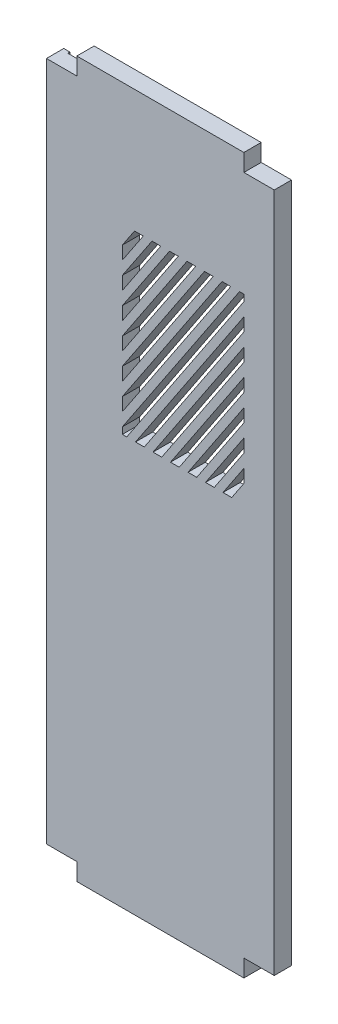
SolidWorks part; units mm, degrees
ref_plane "Front Plane" through (0, 0, 0) normal (0, 0, 1) x (1, 0, 0)
ref_plane "Top Plane" through (0, 0, 0) normal (0, 1, 0) x (1, 0, 0)
ref_plane "Right Plane" through (0, 0, 0) normal (1, 0, 0) x (0, 0, -1)
sketch "Sketch1" plane through (0, 0, 0) normal (0, 0, 1) x (1, 0, 0)
  line L1 (0, 0) -> (75, 0)
  line L2 (0, 0) -> (0, 235.4)
  line L3 (0, 235.4) -> (75, 235.4)
  line L4 (75, 0) -> (75, 235.4)
  dimension "D1" = 235.4
  dimension "D2" = 75
extrude "Boss-Extrude1" add sketch "Sketch1" along normal blind 5.7
sketch "Sketch2" plane through (0, 0, 0) normal (0, 0, -1) x (-1, 0, 0)
  line L2 (-75, 0) -> (-65, 0)
  line L3 (-75, 0) -> (-75, 5.7)
  line L4 (-75, 5.7) -> (-65, 5.7)
  line L6 (-65, 0) -> (-65, 5.7)
  line L7 (0, 0) -> (-10, 0)
  line L8 (0, 0) -> (0, 5.7)
  line L9 (0, 5.7) -> (-10, 5.7)
  line L12 (-10, 0) -> (-10, 5.7)
  line L13 (0, 235.4) -> (-10, 235.4)
  line L14 (0, 235.4) -> (0, 229.7)
  line L15 (0, 229.7) -> (-10, 229.7)
  line L16 (-10, 235.4) -> (-10, 229.7)
  line L17 (-75, 235.4) -> (-65, 235.4)
  line L18 (-75, 235.4) -> (-75, 229.7)
  line L19 (-75, 229.7) -> (-65, 229.7)
  line L20 (-65, 235.4) -> (-65, 229.7)
  dimension "D1" = 5.7
  dimension "D2" = 5.7
  dimension "D3" = 10
  dimension "D4" = 10
  dimension "D5" = 10
  dimension "D6" = 5.7
  dimension "D7" = 5.7
  dimension "D8" = 10
extrude "Cut-Extrude1" cut sketch "Sketch2" against normal blind 5.7
sketch "Sketch3" plane through (0, 0, 5.7) normal (0, 0, 1) x (1, 0, 0)
  line L1 (75, 5.7) -> (75, 229.7) construction
  line L39 (65, 195) -> (25, 135) construction
  line L40 (25, 195) -> (65, 195)
  line L41 (25, 195) -> (25, 135)
  line L42 (25, 135) -> (65, 135)
  line L43 (65, 195) -> (65, 135)
  line L44 (63.5578, 195) -> (25, 137.1633)
  line L45 (65, 192.8367) -> (26.4422, 135)
  line L46 (45, 165) -> (25, 165) construction
  line L47 (45, 165) -> (65, 165) construction
  line L48 (60.6778, 195) -> (25, 141.4833)
  line L49 (57.7978, 195) -> (25, 145.8033)
  line L50 (54.9178, 195) -> (25, 150.1233)
  line L51 (52.0378, 195) -> (25, 154.4433)
  line L52 (49.1578, 195) -> (25, 158.7633)
  line L53 (46.2778, 195) -> (25, 163.0833)
  line L54 (43.3978, 195) -> (25, 167.4033)
  line L55 (40.5178, 195) -> (25, 171.7233)
  line L56 (37.6378, 195) -> (25, 176.0433)
  line L57 (34.7578, 195) -> (25, 180.3633)
  line L58 (31.8778, 195) -> (25, 184.6833)
  line L59 (28.9978, 195) -> (25, 189.0033)
  line L60 (26.1178, 195) -> (25, 193.3233)
  line L61 (65, 188.5167) -> (29.3222, 135)
  line L62 (65, 184.1967) -> (32.2022, 135)
  line L63 (65, 179.8767) -> (35.0822, 135)
  line L64 (65, 175.5567) -> (37.9622, 135)
  line L65 (65, 171.2367) -> (40.8422, 135)
  line L66 (65, 166.9167) -> (43.7222, 135)
  line L67 (65, 162.5967) -> (46.6022, 135)
  line L68 (65, 158.2767) -> (49.4822, 135)
  line L69 (65, 153.9567) -> (52.3622, 135)
  line L70 (65, 149.6367) -> (55.2422, 135)
  line L71 (65, 145.3167) -> (58.1222, 135)
  line L72 (65, 140.9967) -> (61.0022, 135)
  line L73 (65, 136.6767) -> (63.8822, 135)
  line L74 (10, 0) -> (65, 0) construction
  point P79 (43.5578, 165)
  point P82 (46.4422, 165)
  dimension "D7" = 40
  dimension "D8" = 165
  dimension "D9" = 30
  dimension "D10" = 1.2
  dimension "D11" = 2.3963
  dimension "D12" = 2.3963
  dimension "D13" = 2.3963
  dimension "D14" = 2.3963
  dimension "D15" = 2.3963
  dimension "D16" = 2.3963
  dimension "D17" = 2.3963
  dimension "D18" = 2.3963
  dimension "D19" = 2.3963
  dimension "D20" = 2.3963
  dimension "D21" = 2.3963
  dimension "D22" = 2.3963
  dimension "D23" = 2.3963
  dimension "D24" = 2.3963
  dimension "D25" = 2.3963
  dimension "D26" = 2.3963
  dimension "D27" = 2.3963
  dimension "D28" = 2.3963
  dimension "D29" = 2.3963
  dimension "D30" = 2.3963
  dimension "D31" = 2.3963
  dimension "D32" = 2.3963
  dimension "D33" = 2.3963
  dimension "D34" = 2.3963
  dimension "D35" = 2.3963
  dimension "D36" = 2.3963
  dimension "D37" = 60
extrude "Cut-Extrude2" cut sketch "Sketch3" against normal blind 5.7 contours L45 L43 L40 L44 L41 L42 | L40 L49 L41 L48 | L40 L51 L41 L50 | L40 L53 L41 L52 | L40 L55 L41 L54 | L40 L57 L41 L56 | L40 L59 L41 L58 | L62 L43 L61 L42 | L64 L43 L63 L42 | L66 L43 L65 L42 | L68 L43 L67 L42 | L70 L43 L69 L42 | L72 L43 L71 L42 region at (27.7824, 190.8263, 5.7) region at (30.6298, 186.5554, 5.7) region at (33.4993, 182.2511, 5.7) region at (36.3741, 177.9388, 5.7) region at (39.251, 173.6235, 5.7) region at (42.129, 169.3065, 5.7) region at (45, 165, 5.7) region at (47.871, 160.6935, 5.7) region at (50.749, 156.3765, 5.7) region at (53.6259, 152.0612, 5.7) region at (56.5007, 147.7489, 5.7) region at (59.3702, 143.4446, 5.7) region at (62.2176, 139.1737, 5.7)
sketch "Sketch4" plane through (0, 0, 0) normal (0, 0, -1) x (-1, 0, 0)
  line L0 (-10, 229.7) -> (0, 229.7) construction
  line L1 (-5, 229.7) -> (-2, 229.7)
  line L2 (-5, 229.7) -> (-5, 5.7)
  line L3 (-5, 5.7) -> (-2, 5.7)
  line L4 (-2, 229.7) -> (-2, 5.7)
  line L5 (0, 5.7) -> (-10, 5.7) construction
  line L6 (0, 229.7) -> (0, 5.7) construction
  dimension "D1" = 2
  dimension "D2" = 3
extrude "Cut-Extrude3" cut sketch "Sketch4" against normal blind 0.7
